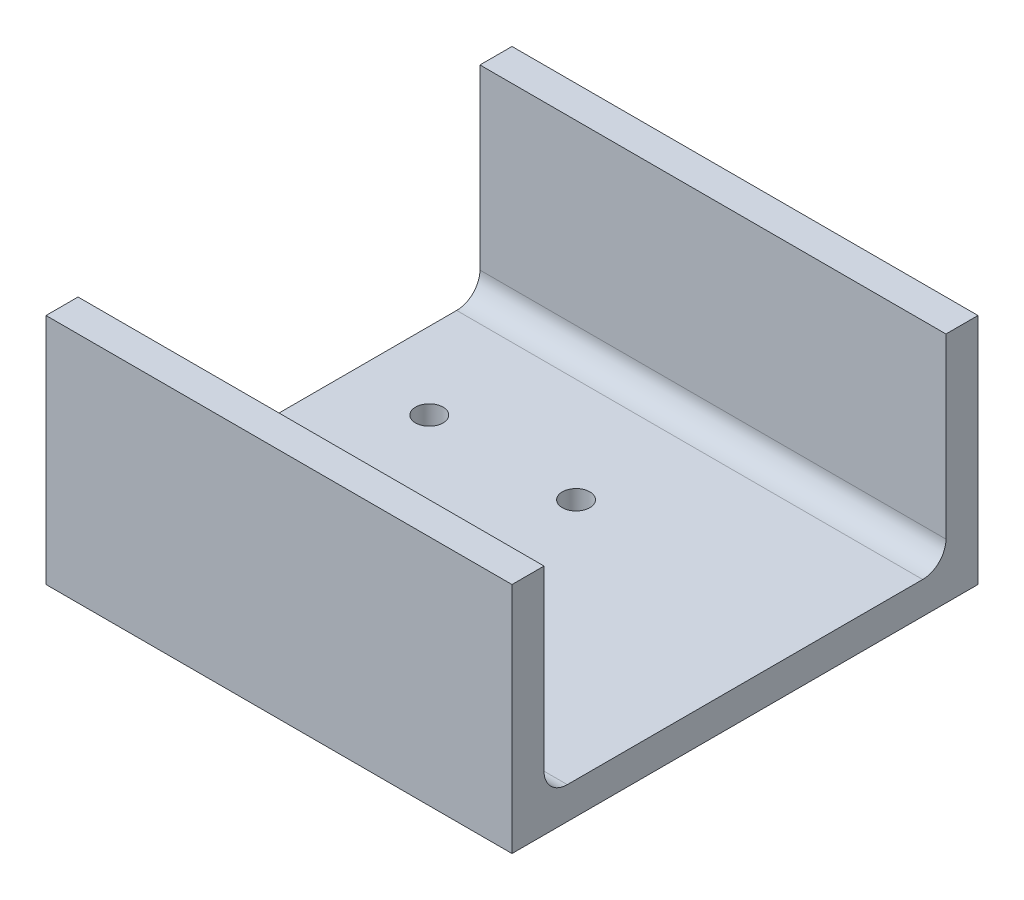
SolidWorks part; units mm, degrees
ref_plane "Front Plane" through (0, 0, 0) normal (0, 0, 1) x (1, 0, 0)
ref_plane "Top Plane" through (0, 0, 0) normal (0, 1, 0) x (1, 0, 0)
ref_plane "Right Plane" through (0, 0, 0) normal (1, 0, 0) x (0, 0, -1)
sketch "Sketch1" plane through (0, 0, 0) normal (1, 0, 0) x (0, 0, -1)
  line L0 (-21.9075, 9.2075) -> (21.9075, 9.2075)
  line L1 (-25.4, -12.7) -> (25.4, -12.7)
  line L2 (-25.4, -12.7) -> (-25.4, 12.7)
  line L3 (-25.4, 12.7) -> (25.4, 12.7)
  line L4 (25.4, -12.7) -> (25.4, 12.7)
  line L5 (-25.4, -12.7) -> (25.4, 12.7) construction
  line L6 (-25.4, 12.7) -> (25.4, -12.7) construction
  line L7 (21.9075, -6.6675) -> (21.9075, 9.2075)
  line L8 (-19.3675, -9.2075) -> (19.3675, -9.2075)
  line L9 (-21.9075, -6.6675) -> (-21.9075, 9.2075)
  line L10 (-21.9075, 9.2075) -> (-21.9075, 12.7)
  line L11 (21.9075, 9.2075) -> (21.9075, 12.7)
  line L12 (21.9075, -9.2075) -> (21.9075, 9.2075) construction
  line L13 (-21.9075, -9.2075) -> (21.9075, -9.2075) construction
  line L14 (-21.9075, -9.2075) -> (-21.9075, 9.2075) construction
  arc A0 (21.9075, -6.6675) -> (19.3675, -9.2075) centre (19.3675, -6.6675) cw
  arc A1 (-19.3675, -9.2075) -> (-21.9075, -6.6675) centre (-19.3675, -6.6675) cw
  point P0 (0, 0)
  dimension "D4" = 2.54
  dimension "D1" = 25.4
  dimension "D2" = 50.8
  dimension "D3" = 3.4925
extrude "Boss-Extrude1" add sketch "Sketch1" along normal blind 50.8 contours L8 A1 L9 L10 L3 L2 L1 L4 L11 L7 A0 region at (0, 1.27, 22.4755)
sketch "Sketch2" plane through (0, -12.7, 0) normal (0, -1, 0) x (1, 0, 0)
  line L0 (25.1124, 0) -> (0, 0) construction
  line L1 (0, 25.4) -> (0, -25.4) construction
  line L2 (50.8, 25.4) -> (0, 25.4) construction
  line L3 (0, 0) -> (16.382, 0)
  line L5 (8.382, 8) -> (24.382, 8) construction
  line L6 (8.382, 8) -> (8.382, -8) construction
  line L7 (8.382, -8) -> (24.382, -8) construction
  line L8 (24.382, 8) -> (24.382, -8) construction
  line L9 (8.382, 8) -> (24.382, -8) construction
  line L10 (8.382, -8) -> (24.382, 8) construction
  circle A0 centre (8.382, 8) radius 1.5
  circle A1 centre (8.382, -8.002) radius 1.5
  circle A2 centre (24.382, -8.002) radius 1.5
  circle A3 centre (24.382, 8) radius 1.5
  point P6 (16.382, 0)
  dimension "D5" = 3
  dimension "D1" = 25.4
  dimension "D2" = 16.382
  dimension "D3" = 16
  dimension "D4" = 16
  dimension "D6" = 2
  dimension "D7" = 2
extrude "Cut-Extrude1" cut sketch "Sketch2" against normal blind 12.954 contours A0 | A3 | A2 | A1 region at (8.382, -12.7, 8) region at (8.382, -12.7, -8.002) region at (24.382, -12.7, -8.002) region at (24.382, -12.7, 8)
